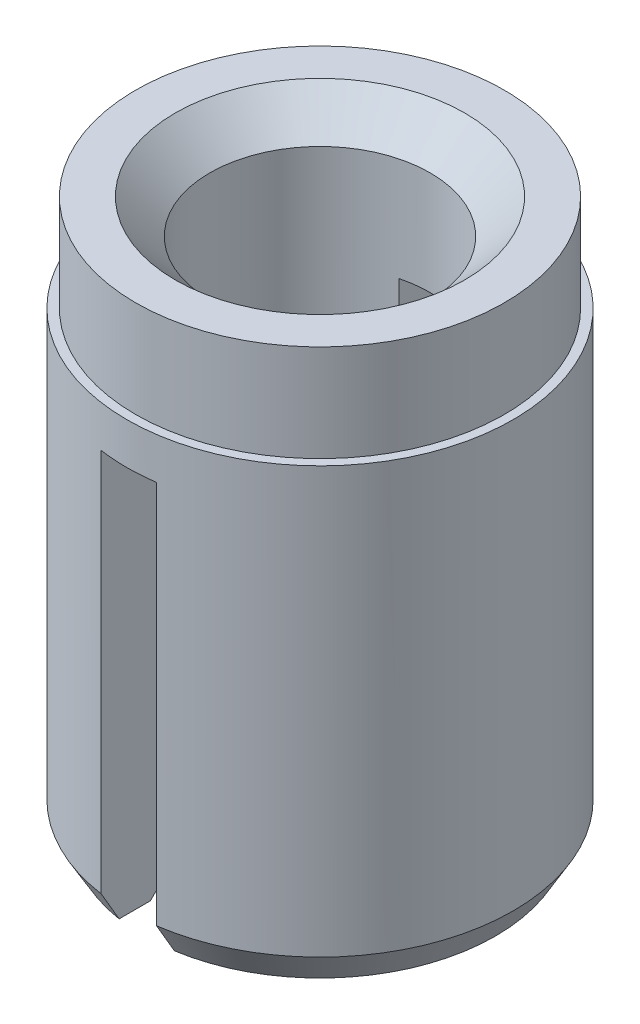
SolidWorks part; units mm, degrees
material "AISI 316 Stainless Steel Sheet (SS)"
ref_plane "Front Plane" through (0, 0, 0) normal (0, 0, 1) x (1, 0, 0)
ref_plane "Top Plane" through (0, 0, 0) normal (0, 1, 0) x (1, 0, 0)
ref_plane "Right Plane" through (0, 0, 0) normal (1, 0, 0) x (0, 0, -1)
sketch "Sketch0" plane through (0, 0, 0) normal (0, 0, 1) x (1, 0, 0)
  line L0 (0, 0) -> (0, -9.525) construction
  line L1 (-2.413, -9.525) -> (2.413, -9.525) construction
  line L2 (-3.175, 0) -> (3.175, 0) construction
  line L3 (-0.4762, -2.3813) -> (0.4763, -2.3813) construction
  line L4 (-3.3274, -1.6669) -> (3.3274, -1.6669) construction
  line L5 (-1.8115, 0.7441) -> (-2.4989, 0.3473) construction
  line L6 (-2.4989, 0.3473) -> (-1.8115, -0.0496) construction
  line L8 (-1.8115, -0.0496) -> (-1.8115, 0.7441) construction
  line L9 (-1.8115, 0.3473) -> (-1.8974, 0.3473) construction
  line L10 (-1.8974, 0.3473) -> (-2.413, 0.3473) construction
  line L11 (-2.413, 0.3473) -> (-2.4989, 0.3473) construction
  line L12 (-2.413, 0.3969) -> (-2.413, 0.2977)
  line L13 (-1.8974, 0) -> (-1.8974, 0.6945) construction
  line L14 (-1.8545, 0.7193) -> (-2.413, 0.3969)
  line L15 (-1.8545, 0.7193) -> (-1.8545, -0.0248)
  line L16 (-1.8545, -0.0248) -> (-2.413, 0.2977)
  point P10 (0, 0)
  point P14 (0, -2.3813)
  point P19 (0, -1.6669)
  point P20 (-3.3274, -9.525)
  point P21 (3.3274, -9.525)
  point P33 (-1.8545, 0.3473)
  dimension "D1" = 0.7937
  dimension "D2" = 0.0992
sketch "Sketch1" plane through (0, 0, 0) normal (0, 1, 0) x (1, 0, 0)
  circle A0 centre (0, 0) radius 3.175
  circle A1 centre (0, 0) radius 3.3274
extrude "Extrude1" add sketch "Sketch1" against normal up to vertex (9.525 mm away) contours A0 up to point (0, -9.525, 0)
sketch "Sketch2" [suppressed] plane through (0, 0, 0) normal (0, 1, 0) x (1, 0, 0)
  circle A2 centre (0, 0) radius 2.413
  point P0 (-2.413, 0)
extrude "Extrude2" add sketch "Sketch1<4>" against normal up to vertex (9.525 mm away) from vertex up to point (0, -9.525, 0) starting at point (0, -1.6669, 0)
sketch "Sketch1<4>" plane through (0, 0, 0) normal (0, 1, 0) x (1, 0, 0) same geometry as "Sketch1"
sketch "Sketch4" plane through (0, 0, 0) normal (0, 1, 0) x (1, 0, 0)
  circle A0 centre (0, 0) radius 1.8974
extrude "Extrude3" cut sketch "Sketch4" against normal up to vertex (9.525 mm away) up to point (0, -9.525, 0)
chamfer "Chamfer1" distance 0.5953 angle 45 2 edges at (0, 0, 1.8974) (0, -9.525, 1.8974)
chamfer "Chamfer2" distance 0.3048 angle 60 1 edges at (0, -9.525, 3.3274) first distance on face at (0, -9.525, 2.4928)
sketch "Sketch8" plane through (0, 0, 0) normal (0, 0, 1) x (1, 0, 0)
  line L1 (-0.4762, -2.3813) -> (0.4763, -2.3813)
  line L2 (-0.4762, -2.3813) -> (-0.4762, -9.525)
  line L3 (-0.4762, -9.525) -> (0.4762, -9.525)
  line L4 (0.4763, -2.3813) -> (0.4762, -9.525)
extrude "Extrude4" cut sketch "Sketch8" along normal through all and the other way through all
curve "Helix/Spiral1" [suppressed] pitch 0.7937 height 10.3187 turns 13 parameters "Height"=10.3187, "Pitch"=0.7937
sketch "Sketch9" [suppressed] plane through (0, 0, 0) normal (0, 0, 1) x (1, 0, 0)
  line L0 (-1.8545, 0.7193) -> (-1.8545, -0.0248) construction
  line L1 (-1.8545, 0.7193) -> (-2.413, 0.3969) construction
  line L2 (-1.8545, -0.0248) -> (-2.413, 0.2977) construction
  line L3 (-2.413, 0.3969) -> (-2.413, 0.2977) construction
  line L4 (-1.8545, 0.7193) -> (-1.8545, -0.0248)
  line L5 (-1.8545, 0.7193) -> (-2.413, 0.3969)
  line L6 (-1.8545, -0.0248) -> (-2.413, 0.2977)
  line L7 (-2.413, 0.3969) -> (-2.413, 0.2977)
sweep "Cut-Sweep2" [suppressed] cut profiles "Sketch9" path "Helix/Spiral1"
sketch "Sketch6" [suppressed] plane through (0, -9.525, 0) normal (0, -1, 0) x (1, 0, 0)
  circle A1 centre (0, 0) radius 3.3274
  circle A2 centre (0, 0) radius 3.3274 construction
  point P3 (0, 3.3274)
curve "Helix/Spiral0" [suppressed] pitch 31.4325 height 7.8581 turns 0.25 parameters "Height"=7.8581, "Pitch"=31.4325
sketch "Sketch7" [suppressed] plane through (0, -9.525, 0) normal (0, -1, 0) x (1, 0, 0)
  line L0 (-0.1524, 3.3274) -> (0, 3.175)
  line L1 (0, 3.175) -> (0.1524, 3.3274)
  line L2 (0.1524, 3.3274) -> (-0.1524, 3.3274)
  circle A0 centre (0, 0) radius 3.175 construction
sweep "Cut-Sweep0" [suppressed] cut profiles "Sketch7" path "Helix/Spiral0"
mirror "Mirror1" [suppressed] about plane through (0, 0, 0) normal (0, 0, 1)
pattern_circular "CirPattern0" [suppressed] count 20 over 360 of bodies 122
equation "\"Height@Helix/Spiral1\" = \"Pitch@Helix/Spiral1\" + \"L@Sketch0\""
equation "\"D1@Chamfer1\" = \"Pitch@Helix/Spiral1\" * 6 / 8"
equation "\"Height@Helix/Spiral0\" = \"Knurl@Sketch0\""
equation "\"Pitch@Helix/Spiral0\" = \"Height@Helix/Spiral0\"  * 4"
equation "\"D1@Chamfer2\" =  ( \"B@Sketch0\" - \"A@Sketch0\" )  / 1"
equation "\"Slot Height@Sketch0\"=\"L@Sketch0\"*.75"
equation "\"Knurl@Sketch0\"=\"L@Sketch0\"*.825"
equation "\"Slot Width@Sketch0\"=\"L@Sketch0\"*.1"
equation "\"D1@Sketch0\"=\"Pitch@Helix/Spiral1\""
equation "\"D2@Sketch0\"=\"Pitch@Helix/Spiral1\"/8"
